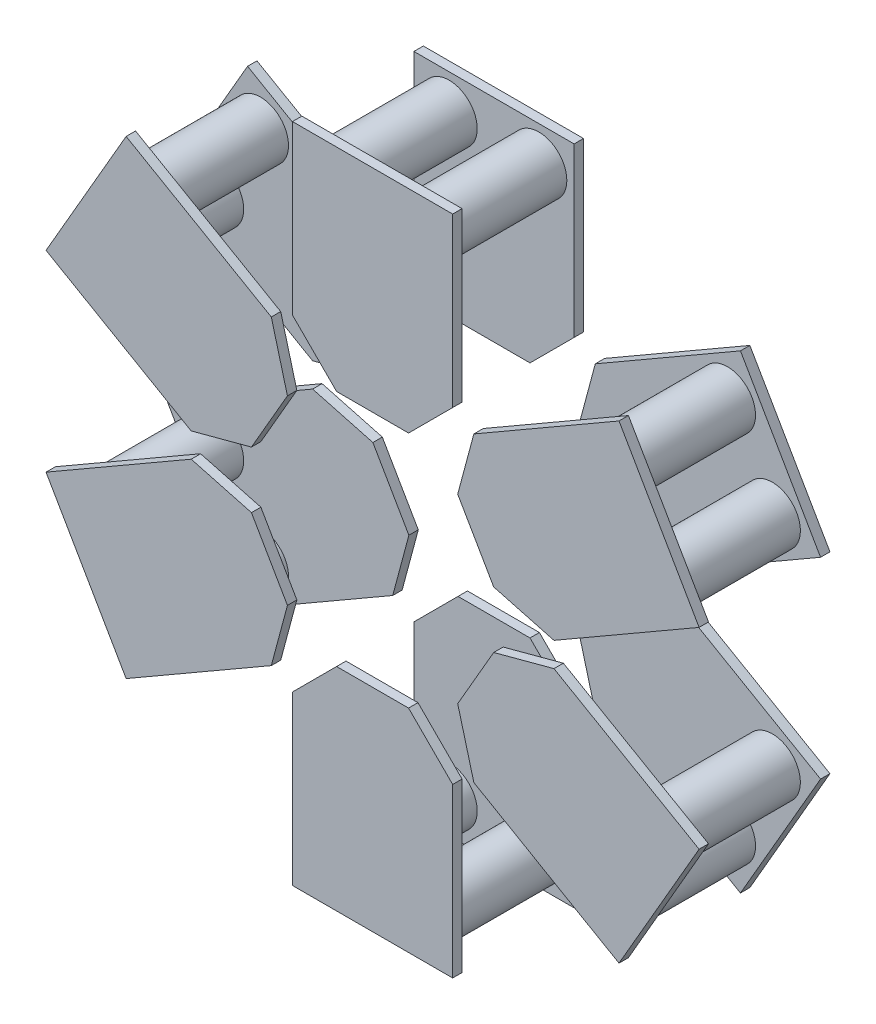
SolidWorks part; units mm, degrees
ref_plane "Front Plane" through (0, 0, 0) normal (0, 0, 1) x (1, 0, 0)
ref_plane "Top Plane" through (0, 0, 0) normal (0, 1, 0) x (1, 0, 0)
ref_plane "Right Plane" through (0, 0, 0) normal (1, 0, 0) x (0, 0, -1)
sketch "Sketch2" plane through (0, 0, 0) normal (0, 0, 1) x (1, 0, 0)
  line L0 (-5.08, 0) -> (5.08, 0)
  circle A0 centre (5.08, 0) radius 3.175
  circle A1 centre (-5.08, 0) radius 3.175
  point P4 (0, 0)
  dimension "D1" = 6.35
  dimension "D2" = 6.35
  dimension "D3" = 10.16
extrude "Boss-Extrude1" add sketch "Sketch2" along normal blind 12.7 contours A1 | A0 region at (5.08, 3.0852, 0) region at (-8.1652, 0, 0)
sketch "Sketch3" plane through (0, 0, 12.7) normal (0, 0, 1) x (1, 0, 0)
  line L0 (5.08, 0) -> (-5.08, 0) construction
  line L1 (0, 0) -> (0, -8) construction
  line L3 (9.08, 4) -> (-9.08, 4)
  line L4 (9.08, 4) -> (9.08, -20)
  line L5 (9.08, -20) -> (-9.08, -20)
  line L6 (-9.08, 4) -> (-9.08, -20)
  line L7 (9.08, 4) -> (-9.08, -20) construction
  line L8 (9.08, -20) -> (-9.08, 4) construction
  dimension "D1" = 8
  dimension "D2" = 4
  dimension "D3" = 4
extrude "Boss-Extrude2" add sketch "Sketch3" along normal blind 1.0668 separate body
ref_plane "Plane1" through (0, 0, 6.35) normal (0, 0, 1) x (1, 0, 0)
mirror "Mirror1" about plane through (0, 0, 6.35) normal (0, 0, 1) of bodies 105
chamfer "Chamfer1" distance 5 angle 45 2 edges at (9.08, -20, 13.2334) (-9.08, -20, 13.2334)
chamfer "Chamfer2" distance 5 angle 45 2 edges at (9.08, -20, -0.5334) (-9.08, -20, -0.5334)
sketch "Sketch4" plane through (0, 0, 0) normal (0, 0, 1) x (1, 0, 0)
  line L0 (0, -20) -> (0, -31.5) construction
  line L1 (-4.08, -20) -> (4.08, -20) construction
  circle A0 centre (0, -31.5) radius 11
  dimension "D2" = 22
  dimension "D1" = 11.5
sketch "Sketch5" plane through (0, 0, 0) normal (1, 0, 0) x (0, 0, -1)
  line L0 (0, -31.5) -> (-22.7792, -31.5)
pattern_circular "CirPattern1" count 6 over 360 about axis through (0, -31.5, 0) along (0, 0, 1) reverse direction yes of bodies 106 101 102 105
sketch "Sketch6" plane through (0, 0, 13.7668) normal (0, 0, 1) x (1, 0, 0)
  line L0 (1.8395, -23.6165) -> (14.0589, -10.2145)
  line L1 (14.0589, -10.2145) -> (10.9055, 5.2897)
  line L2 (10.9055, 5.2897) -> (-1.0511, 8.5745)
  line L3 (-1.0511, 8.5745) -> (-14.6502, 8.0489)
  line L4 (-14.6502, 8.0489) -> (-15.5084, -0.0826)
  line L5 (-15.5084, -0.0826) -> (-10.0515, -14.6818)
  line L6 (-10.0515, -14.6818) -> (-2.0366, -23.6165)
  line L7 (-2.0366, -23.6165) -> (1.8395, -23.6165)
extrude "Cut-Extrude1" cut sketch "Sketch6" against normal through all both and the other way through all flip side to cut
sketch "Sketch7" plane through (0, 0, 13.7668) normal (0, 0, 1) x (1, 0, 0)
  line L0 (0, -20) -> (0, -33.5) construction
  line L1 (-4.08, -20) -> (4.08, -20) construction
  circle A0 centre (0, -33.5) radius 5.1296
  dimension "D1" = 13.5
ref_axis "Axis1" through (0, -33.5, 13.7668) along (0, 0, 1)
pattern_circular "CirPattern2" count 6 over 360 about axis through (0, -33.5, 13.7668) along (0, 0, 1) of bodies 101 106 102 105
